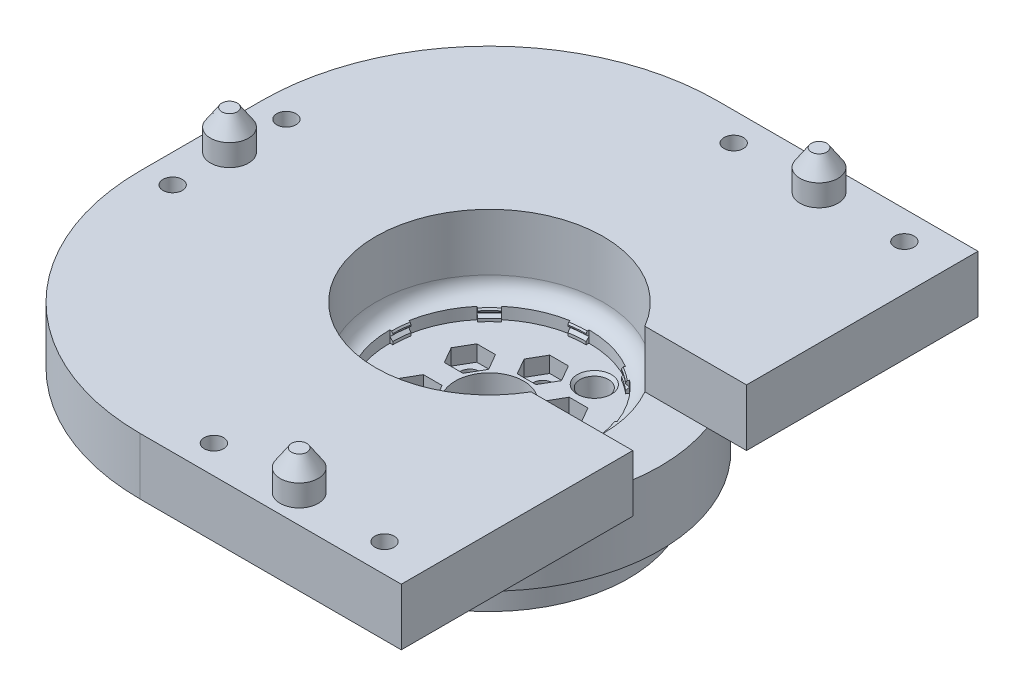
SolidWorks part; units mm, degrees
note: The reader was unsure of these and kept them because the rebuilt part matched: shared geometry of "Sketch3<2>", "Sketch3<4>".
ref_plane "Front Plane" through (0, 0, 0) normal (0, 0, 1) x (1, 0, 0)
ref_plane "Top Plane" through (0, 0, 0) normal (0, 1, 0) x (1, 0, 0)
ref_plane "Right Plane" through (0, 0, 0) normal (1, 0, 0) x (0, 0, -1)
sketch "Sketch1" plane through (0, 0, 0) normal (0, 0, 1) x (1, 0, 0)
  line L0 (6, 0) -> (19.8, 0)
  line L1 (19.8, 0) -> (19.8, 0.2)
  line L2 (19.8, 0.2) -> (24.5, 0.2)
  line L3 (24.5, 0.2) -> (24.5, 7.2)
  line L4 (24.5, 7.2) -> (30, 7.2)
  line L5 (30, 7.2) -> (30, 30)
  line L11 (0, -743.6468) -> (0, 36438.6946) construction
  line L12 (6, 0) -> (6, 15)
  line L13 (30, 30) -> (20, 30)
  line L14 (20, 30) -> (20, 20)
  line L15 (6, 15) -> (17, 15)
  line L16 (17, 15) -> (17, 17)
  line L17 (17, 17) -> (20, 17) construction
  line L18 (20, 17) -> (20, 20) construction
  line L19 (17, 15.5) -> (17.5, 16)
  line L20 (17.5, 16) -> (17, 16.5)
  line L21 (17, 16.7) -> (17.2, 17.0067)
  arc A0 (17, 17) -> (20, 20) centre (17, 20) ccw
  dimension "D1" = 12
  dimension "D2" = 39.6
  dimension "D3" = 0.2
  dimension "D4" = 49
  dimension "D5" = 7
  dimension "D6" = 30
  dimension "D9" = 34
  dimension "D7" = 10
  dimension "D10" = 30
  dimension "D8" = 15
  dimension "D11" = 2
  dimension "D12" = 0.5
  dimension "D14" = 1
  dimension "D13" = 1
  dimension "D15" = 0.2
  dimension "D16" = 0.2
revolve "Revolve1" add sketch "Sketch1" angle 360 about L11
sketch "Sketch2" plane through (0, 15, 0) normal (0, 1, 0) x (1, 0, 0)
  line L0 (0, 0) -> (0, 17.5) construction
  line L1 (0, 0) -> (8.75, 15.1554) construction
  line L2 (8.5, 14.7224) -> (8.75, 15.1554)
  line L3 (0, 17) -> (0, 17.5)
  circle A0 centre (0, 0) radius 17.5 construction
  arc A1 (8.75, 15.1554) -> (0, 17.5) centre (0, 0) ccw
  circle A2 centre (0, 0) radius 17 construction
  arc A3 (8.5, 14.7224) -> (0, 17) centre (0, 0) ccw
  dimension "D1" = 30
extrude "Cut-Extrude1" cut sketch "Sketch2" along normal up to surface (2 mm away)
pattern_circular "CirPattern1" count 9 over 360 about axis through (0, 0, 0) along (0, 1, 0) of "Cut-Extrude1"
sketch "Sketch3" plane through (0, 15, 0) normal (0, 1, 0) x (1, 0, 0)
  line L0 (9.7731, 1.8425) -> (11.4185, 4.6925)
  line L1 (3.2909, 9.385) -> (1.6454, 12.235)
  line L2 (1.6454, 12.235) -> (-1.6454, 12.235)
  line L3 (-1.6454, 12.235) -> (-3.2909, 9.385)
  line L4 (-3.2909, 9.385) -> (-1.6454, 6.535)
  line L5 (-1.6454, 6.535) -> (1.6454, 6.535)
  line L6 (1.6454, 6.535) -> (3.2909, 9.385)
  line L7 (11.4185, 4.6925) -> (9.7731, 7.5425)
  line L8 (9.7731, 7.5425) -> (6.4822, 7.5425)
  line L9 (6.4822, 7.5425) -> (4.8368, 4.6925)
  line L10 (4.8368, 4.6925) -> (6.4822, 1.8425)
  line L11 (6.4822, 1.8425) -> (9.7731, 1.8425)
  line L12 (6.4822, -7.5425) -> (9.7731, -7.5425)
  line L13 (9.7731, -7.5425) -> (11.4185, -4.6925)
  line L14 (11.4185, -4.6925) -> (9.7731, -1.8425)
  line L15 (9.7731, -1.8425) -> (6.4822, -1.8425)
  line L16 (6.4822, -1.8425) -> (4.8368, -4.6925)
  line L17 (4.8368, -4.6925) -> (6.4822, -7.5425)
  line L18 (-3.2909, -9.385) -> (-1.6454, -12.235)
  line L19 (-1.6454, -12.235) -> (1.6454, -12.235)
  line L20 (1.6454, -12.235) -> (3.2909, -9.385)
  line L21 (3.2909, -9.385) -> (1.6454, -6.535)
  line L22 (1.6454, -6.535) -> (-1.6454, -6.535)
  line L23 (-1.6454, -6.535) -> (-3.2909, -9.385)
  line L24 (-9.7731, -1.8425) -> (-11.4185, -4.6925)
  line L25 (-11.4185, -4.6925) -> (-9.7731, -7.5425)
  line L26 (-9.7731, -7.5425) -> (-6.4822, -7.5425)
  line L27 (-6.4822, -7.5425) -> (-4.8368, -4.6925)
  line L28 (-4.8368, -4.6925) -> (-6.4822, -1.8425)
  line L29 (-6.4822, -1.8425) -> (-9.7731, -1.8425)
  line L30 (-6.4822, 7.5425) -> (-9.7731, 7.5425)
  line L31 (-9.7731, 7.5425) -> (-11.4185, 4.6925)
  line L32 (-11.4185, 4.6925) -> (-9.7731, 1.8425)
  line L33 (-9.7731, 1.8425) -> (-6.4822, 1.8425)
  line L34 (-6.4822, 1.8425) -> (-4.8368, 4.6925)
  line L35 (-4.8368, 4.6925) -> (-6.4822, 7.5425)
  line L36 (-1000, 0) -> (49000, 0) construction
  line L37 (0, 0) -> (25000, 43301.2702) construction
  circle A0 centre (0, 0) radius 9.385 construction
  circle A1 centre (0, 9.385) radius 2.85 construction
  circle A2 centre (0, 0) radius 9.385 construction
  circle A3 centre (0, 0) radius 9.385 construction
  circle A4 centre (0, 0) radius 9.385 construction
  circle A5 centre (0, 0) radius 9.385 construction
  circle A6 centre (0, 0) radius 9.385 construction
  circle A7 centre (0, 9.385) radius 1.7
  circle A8 centre (8.1276, 4.6925) radius 1.7
  circle A9 centre (8.1276, -4.6925) radius 1.7
  circle A10 centre (0, -9.385) radius 1.7
  circle A11 centre (-8.1276, -4.6925) radius 1.7
  circle A12 centre (-8.1276, 4.6925) radius 1.7
  circle A13 centre (0, 0) radius 13.5 construction
  circle A14 centre (6.75, 11.6913) radius 2.5
  circle A15 centre (-6.75, -11.6913) radius 2.5
  point P49 (0, 0)
  dimension "D1" = 18.77
  dimension "D2" = 5.7
  dimension "D4" = 3.4
  dimension "D5" = 27
  dimension "D7" = 5
  dimension "D6" = 60
  dimension "D3" = 6
extrude "Cut-Extrude2" cut sketch "Sketch3" against normal blind 2.8
extrude "Cut-Extrude3" cut sketch "Sketch3<2>" against normal through all contours A7 | A8 | A9 | A10 | A11 | A12
sketch "Sketch3<2>" plane through (0, 15, 0) normal (0, 1, 0) x (1, 0, 0) same geometry as "Sketch3"
extrude "Cut-Extrude4" cut sketch "Sketch3<4>" against normal blind 5 contours A14 | A15
sketch "Sketch3<4>" plane through (0, 15, 0) normal (0, 1, 0) x (1, 0, 0) same geometry as "Sketch3"
chamfer "Chamfer1" distance 0.5 angle 45 2 edges at (6.75, 15, -9.1913) (-6.75, 15, 14.1913)
sketch "Sketch6" plane through (0, 30, 0) normal (0, 1, 0) x (1, 0, 0)
  line L0 (5, 29.5804) -> (5, -29.5804)
  line L1 (0, -1000) -> (0, 49000) construction
  line L2 (5, 10) -> (28.2843, 10)
  line L3 (-1000, 0) -> (49000, 0) construction
  line L4 (5, -10) -> (28.2843, -10)
  line L5 (-5, 29.5804) -> (-5, -29.5804)
  circle A0 centre (0, 0) radius 30 construction
  circle A2 centre (0, 0) radius 30
  circle A3 centre (0, 0) radius 30
  circle M6 centre (0, 0) radius 20
  circle M7 centre (0, 0) radius 30
  dimension "D1" = 10
  dimension "D2" = 20
  dimension "D3" = 0
extrude "Cut-Extrude5" cut sketch "Sketch6" against normal blind 10 contours L4 L2 M6 M7
sketch "Sketch7" plane through (0, 30, 0) normal (0, 1, 0) x (1, 0, 0)
  line L0 (0, 30.5) -> (35, 30.5) construction
  line L1 (35, 30.5) -> (35, -30.5) construction
  line L2 (35, -30.5) -> (0, -30.5) construction
  line L3 (35.2, -30.7) -> (0, -30.7)
  line L4 (35.2, 30.7) -> (35.2, -30.7)
  line L5 (0, 30.7) -> (35.2, 30.7)
  line L6 (35.2, 30.7) -> (35.2, 50.7)
  line L7 (35.2, 50.7) -> (-10.7, 50.7)
  line L8 (-50.7, 10.7) -> (-50.7, -10.7)
  line L9 (-10.7, -50.7) -> (35.2, -50.7)
  line L10 (35.2, -50.7) -> (35.2, -30.7)
  line L11 (28.2843, 10) -> (35.2, 10)
  line L12 (28.2843, -10) -> (35.2, -10)
  line L13 (17.3205, 10) -> (28.2843, 10)
  line L14 (28.2843, -10) -> (17.3205, -10)
  line L15 (17.3205, 10) -> (28.2843, 10)
  line L16 (28.2843, -10) -> (17.3205, -10)
  arc A0 (0, 30.5) -> (0, -30.5) centre (0, 0) ccw construction
  arc A1 (0, 30.7) -> (0, -30.7) centre (0, 0) ccw
  arc A2 (-50.7, -10.7) -> (-10.7, -50.7) centre (-10.7, -10.7) ccw
  arc A3 (-10.7, 50.7) -> (-50.7, 10.7) centre (-10.7, 10.7) ccw
  arc A6 (17.3205, 10) -> (17.3205, -10) centre (0, 0) ccw
  arc A7 (28.2843, 10) -> (28.2843, -10) centre (0, 0) ccw
  arc A8 (17.3205, 10) -> (17.3205, -10) centre (0, 0) ccw
  arc A9 (28.2843, 10) -> (28.2843, -10) centre (0, 0) ccw
  arc M4 (17.3205, -10) -> (17.3205, 10) centre (0, 0) cw
  line M5 (17.3205, 10) -> (28.2843, 10)
  arc M6 (28.2843, 10) -> (28.2843, -10) centre (0, 0) ccw
  line M7 (28.2843, -10) -> (17.3205, -10)
  dimension "D1" = 61
  dimension "D5" = 40
  dimension "D7" = 30.7
  dimension "D2" = 35
  dimension "D3" = 20
  dimension "D4" = 20
  dimension "D6" = 0.2
  dimension "D8" = 0
other "AlignGroup1"
extrude "Boss-Extrude1" add sketch "Sketch7" against normal blind 10 contours M7 M4 M5 M6 | L5 A1 L3 L4 L12 L11 M6 | L7 A3 L8 A2 L9 L10 L3 A1 L5 L6
sketch "Sketch8" plane through (0, 30, 0) normal (0, 1, 0) x (1, 0, 0)
  line L6 (35.2, 45.7) -> (-10.7, 45.7)
  line L7 (-45.7, 10.7) -> (-45.7, -10.7)
  line L8 (-10.7, -45.7) -> (35.2, -45.7)
  line L9 (35.2, 45.7) -> (-10.7, 45.7)
  line L10 (-45.7, 10.7) -> (-45.7, -10.7)
  line L11 (-10.7, -45.7) -> (35.2, -45.7)
  arc A4 (-10.7, 45.7) -> (-45.7, 10.7) centre (-10.7, 10.7) ccw
  arc A5 (-45.7, -10.7) -> (-10.7, -45.7) centre (-10.7, -10.7) ccw
  arc A6 (-10.7, 45.7) -> (-45.7, 10.7) centre (-10.7, 10.7) ccw
  arc A7 (-45.7, -10.7) -> (-10.7, -45.7) centre (-10.7, -10.7) ccw
  point P0 (12.25, -45.7)
  point P1 (-45.7, 0)
  point P2 (12.25, 45.7)
  dimension "D1" = 5
ref_plane "Plane1" through (0, 0, 45.7) normal (0, 0, 1) x (1, 0, 0)
sketch "Sketch9" plane through (0, 0, 45.7) normal (0, 0, 1) x (1, 0, 0)
  line L0 (12.25, -970) -> (12.25, 49030) construction
  line L1 (15.6, 30) -> (15.6, 33.8)
  line L2 (-10.7, 30) -> (35.2, 30) construction
  line L3 (15.6, 33.8) -> (13.6, 36.8)
  line L4 (13.6, 36.8) -> (12.25, 36.8)
  line L5 (12.25, 36.8) -> (12.25, 30)
  line L6 (12.25, 30) -> (15.6, 30)
  dimension "D1" = 6.7
  dimension "D2" = 3.8
  dimension "D3" = 6.8
  dimension "D4" = 2.7
revolve "Revolve2" add sketch "Sketch9" angle 360 about L0
pattern_sketch "Sketch-Pattern1" of "Revolve2" driven by "Sketch8"
sketch "Sketch10" plane through (0, 30, 0) normal (0, 1, 0) x (1, 0, 0)
  line L0 (-10.7, -45.7) -> (35.2, -45.7) construction
  line L1 (-45.7, 10.7) -> (-45.7, -10.7) construction
  line L2 (-1000, 0) -> (49000, 0) construction
  circle A0 centre (27.25, -45.7) radius 1.7
  circle A1 centre (-2.75, -45.7) radius 1.7
  circle A2 centre (12.25, -45.7) radius 3.35 construction
  circle A3 centre (12.25, -45.7) radius 3.35 construction
  circle A4 centre (-45.7, -10) radius 1.7
  circle A6 centre (-45.7, 0) radius 3.35 construction
  circle A7 centre (-45.7, 10) radius 1.7
  circle A8 centre (-2.75, 45.7) radius 1.7
  circle A9 centre (27.25, 45.7) radius 1.7
  dimension "D1" = 3.4
  dimension "D3" = 15
  dimension "D4" = 15
  dimension "D2" = 10
extrude "Cut-Extrude6" cut sketch "Sketch10" against normal through all
sketch "Sketch11" plane through (0, 20, 0) normal (0, -1, 0) x (1, 0, 0)
  line L0 (-1000, 0) -> (49000, 0) construction
  line L1 (30.5986, 45.7) -> (28.9243, 48.6)
  line L2 (28.9243, 48.6) -> (25.5757, 48.6)
  line L3 (25.5757, 48.6) -> (23.9014, 45.7)
  line L4 (23.9014, 45.7) -> (25.5757, 42.8)
  line L5 (25.5757, 42.8) -> (28.9243, 42.8)
  line L6 (28.9243, 42.8) -> (30.5986, 45.7)
  line L7 (0.5986, 45.7) -> (-1.0757, 48.6)
  line L8 (-1.0757, 48.6) -> (-4.4243, 48.6)
  line L9 (-4.4243, 48.6) -> (-6.0986, 45.7)
  line L10 (-6.0986, 45.7) -> (-4.4243, 42.8)
  line L11 (-4.4243, 42.8) -> (-1.0757, 42.8)
  line L12 (-1.0757, 42.8) -> (0.5986, 45.7)
  line L13 (-45.7, 13.3486) -> (-48.6, 11.6743)
  line L14 (-48.6, 11.6743) -> (-48.6, 8.3257)
  line L15 (-48.6, 8.3257) -> (-45.7, 6.6514)
  line L16 (-45.7, 6.6514) -> (-42.8, 8.3257)
  line L17 (-42.8, 8.3257) -> (-42.8, 11.6743)
  line L18 (-42.8, 11.6743) -> (-45.7, 13.3486)
  line L19 (-42.8, -11.6743) -> (-45.7, -13.3486)
  line L20 (-42.8, -8.3257) -> (-42.8, -11.6743)
  line L21 (-45.7, -6.6514) -> (-42.8, -8.3257)
  line L22 (-48.6, -8.3257) -> (-45.7, -6.6514)
  line L23 (-48.6, -11.6743) -> (-48.6, -8.3257)
  line L24 (-45.7, -13.3486) -> (-48.6, -11.6743)
  line L25 (-1.0757, -42.8) -> (0.5986, -45.7)
  line L26 (-4.4243, -42.8) -> (-1.0757, -42.8)
  line L27 (-6.0986, -45.7) -> (-4.4243, -42.8)
  line L28 (-4.4243, -48.6) -> (-6.0986, -45.7)
  line L29 (-1.0757, -48.6) -> (-4.4243, -48.6)
  line L30 (0.5986, -45.7) -> (-1.0757, -48.6)
  line L31 (28.9243, -42.8) -> (30.5986, -45.7)
  line L32 (25.5757, -42.8) -> (28.9243, -42.8)
  line L33 (23.9014, -45.7) -> (25.5757, -42.8)
  line L34 (25.5757, -48.6) -> (23.9014, -45.7)
  line L35 (28.9243, -48.6) -> (25.5757, -48.6)
  line L36 (30.5986, -45.7) -> (28.9243, -48.6)
  circle A0 centre (27.25, 45.7) radius 2.9 construction
  circle A1 centre (-2.75, 45.7) radius 2.9 construction
  circle A2 centre (-45.7, 10) radius 2.9 construction
  circle A3 centre (-45.7, -10) radius 2.9 construction
  circle A4 centre (-2.75, -45.7) radius 2.9 construction
  circle A5 centre (27.25, -45.7) radius 2.9 construction
  dimension "D1" = 5.8
extrude "Cut-Extrude7" cut sketch "Sketch11" against normal blind 3
equation "\"wire_input_hole_dia\" = 12mm"
equation "\"bolt_retaining_disk_dia\" = 34mm"
equation "\"D1@Sketch1\"=\"wire_input_hole_dia\""
equation "\"D9@Sketch1\"=\"bolt_retaining_disk_dia\""
equation "\"V-slot_depth\" = 0.5mm"
equation "\"V-slot-width\" = 1mm"
equation "\"Clearance_offset\" = 0.2mm"
equation "\"interference_offset\" = 0.1mm"
equation "\"Retaining_disk_thickness\" = 2mm"
equation "\"D11@Sketch1\"=\"Retaining_disk_thickness\""
equation "\"D14@Sketch1\"=\"V-slot-width\""
equation "\"D12@Sketch1\"=\"V-slot_depth\""
equation "\"D4@Sketch10\"=\"D3@Sketch10\""
